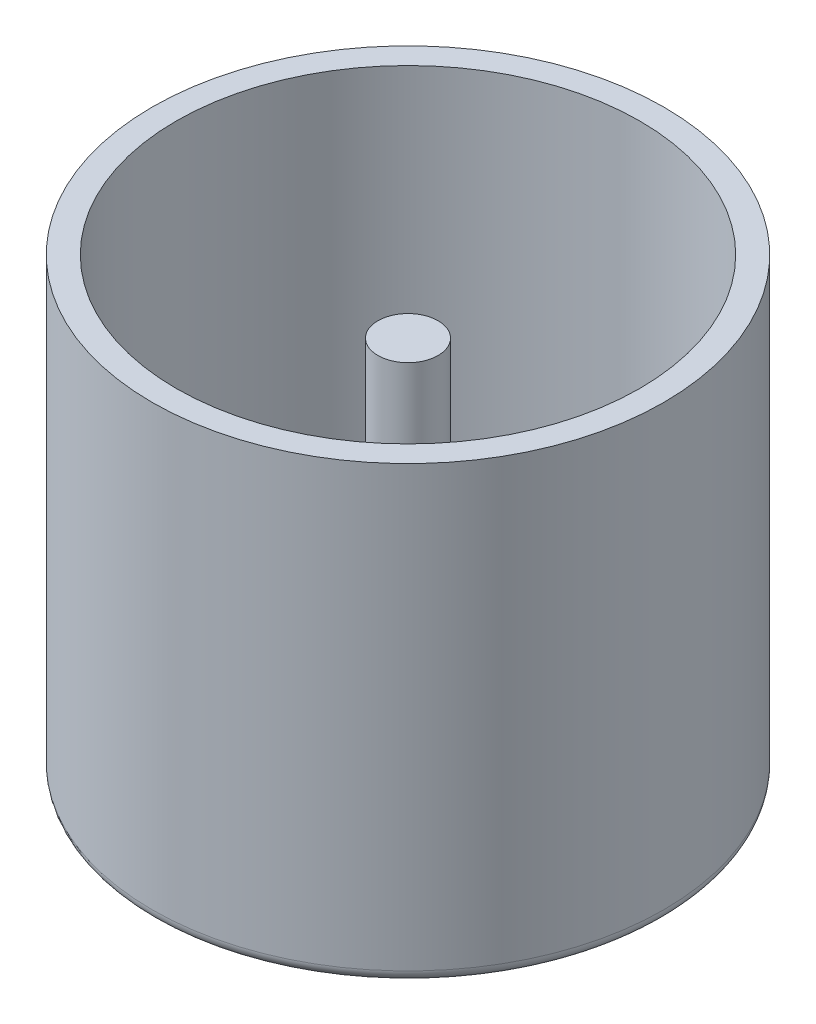
SolidWorks part; units mm, degrees
ref_plane "Front Plane" through (0, 0, 0) normal (0, 0, 1) x (1, 0, 0)
ref_plane "Top Plane" through (0, 0, 0) normal (0, 1, 0) x (1, 0, 0)
ref_plane "Right Plane" through (0, 0, 0) normal (1, 0, 0) x (0, 0, -1)
sketch "Sketch1" plane through (0, 0, 0) normal (0, 1, 0) x (1, 0, 0)
  circle A0 centre (0, 0) radius 53.975
  dimension "D1" = 107.95
extrude "Boss-Extrude1" add sketch "Sketch1" along normal blind 95.25 contours A0
shell "Shell1" thickness 5.08 removed face at (0, 95.25, 53.975)
sketch "Sketch2" plane through (0, 5.08, 0) normal (0, 1, 0) x (1, 0, 0)
  circle A0 centre (0, 0) radius 6.35
  dimension "D1" = 12.7
extrude "Boss-Extrude2" add sketch "Sketch2" along normal blind 74.93
sketch "Sketch3" plane through (0, 80.01, 0) normal (0, 1, 0) x (1, 0, 0)
  line L0 (-1.5875, -6.1484) -> (-1.5875, -2.7496)
  line L1 (1.5875, -6.1484) -> (1.5875, -2.7496)
  line L2 (0, 0) -> (0, -10.1294) construction
  circle A2 centre (0, 0) radius 3.175
  circle A3 centre (0, 0) radius 6.35 construction
  circle A4 centre (0, 0) radius 6.35 construction
  dimension "D1" = 6.35
  dimension "D2" = 3.175
  dimension "D3" = 1.5875
ref_axis "Axis2" through (0, 80.01, 0) along (0, -1, 0)
ref_axis "Axis3" through (0, 80.01, 0) along (0, -1, 0)
fillet "Fillet1" radius 2.54 1 edges at (0, 0, 53.975)
equation "\"chalk_length\"= 2.95in"
equation "\"chalk_diameter\"= 0.47in"
equation "\"drum_diameter\"= 4.25in"
equation "\"drum_thickness\" = 0.2in"
equation "\"drum_height\"= 3.75in"
equation "\"D1@Sketch1\"=\"drum_diameter\""
equation "\"D1@Boss-Extrude1\"=\"drum_height\""
equation "\"D1@Shell1\"=\"drum_thickness\""
equation "\"axis_diameter\" = 0.5in"
equation "\"D1@Sketch2\"=\"axis_diameter\""
equation "\"axis_grips\"= \"axis_diameter\" / 4"
equation "\"axis_insert_gap\"= \"axis_diameter\" / 4"
equation "\"D1@Sketch3\"=\"axis_diameter\"/2"
equation "\"D2@Sketch3\"=\"axis_insert_gap\""
equation "\"D3@Sketch3\"=\"axis_insert_gap\"/2"
equation "\"carousel_height\" = 0.4in"
equation "\"D1@Boss-Extrude2\"=\"drum_height\" - 2*\"carousel_height\""
equation "\"tight_fit\" = 0.005in"
equation "\"normal_fit\" = 0.010in"
equation "\"loose_fit\" = 0.020in"
equation "\"top_diameter\"= \"drum_diameter\" - 2 * \"drum_thickness\" - \"loose_fit\""
equation "\"top_thickness\"= 0.2in"
equation "\"hexagonal_diameter\"= 0.75in'Can't be less than axis_diaemeter + top_thickness. Hexagonal diameter for top interface and chalk_slot"
equation "\"hexagonal_female_diameter\"= 0.10in'All hexagons use inscribed unless otherwise explicit"
equation "\"hexagonal_female_spacing\"= 0.10in"
equation "\"hexagonal_female_height\"= 0.15in"
equation "\"chalk_slot_diameter\"= 0.75in"
equation "\"chalk_slot_height\"= 2.95in"
equation "\"chalk_padding_gap\"= 0.10in"
equation "\"cap_height\" = 0.5in"
equation "\"cap_depth\" = 0.5in"
